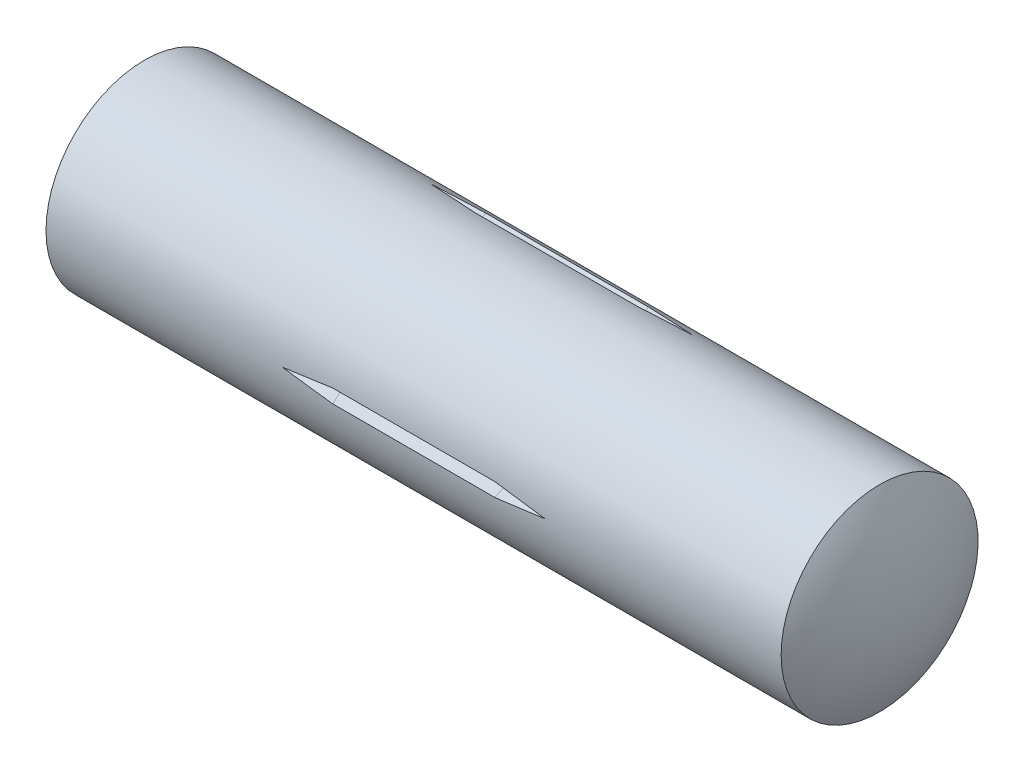
SolidWorks part; units mm, degrees
ref_plane "Plane1" through (0, 0, 0) normal (0, 0, 1) x (1, 0, 0)
ref_plane "Plane2" through (0, 0, 0) normal (0, 1, 0) x (1, 0, 0)
ref_plane "Plane3" through (0, 0, 0) normal (1, 0, 0) x (0, 0, -1)
sketch "Sketch1" plane through (0, 0, 0) normal (0, 0, 1) x (1, 0, 0)
  line L0 (-57, 0) -> (60, 0) construction
  line L1 (-50, 0) -> (-50, 1.25)
  line L2 (-46.6819, 12.5) -> (46.6506, 12.5)
  line L3 (-50, 0) -> (50, 0)
  arc A0 (-46.6819, 12.5) -> (-50, 1.25) centre (-25.0313, 0) ccw
  arc A1 (50, 0) -> (46.6506, 12.5) centre (25, 0) ccw
  dimension "D1" = 25
  dimension "D2" = 25
  dimension "Length" = 100
  dimension "D3" = 2.5
revolve "Base-Revolve" add sketch "Sketch1" angle 360 about L0
sketch "Sketch3" plane through (0, 0, 0) normal (0, 1, 0) x (1, 0, 0)
  line L0 (0, 0) -> (60, 0) construction
  line L1 (-57, 0) -> (60, 0) construction
  line L2 (-16.6667, -12.5) -> (-10.4167, -11.25)
  line L3 (-10.4167, -11.25) -> (10.4167, -11.25)
  line L4 (10.4167, -11.25) -> (16.6667, -12.5)
  dimension "D1" = 25
  dimension "D2" = 33.3333
  dimension "D3" = 16.6667
  dimension "D4" = 22.5
  dimension "D5" = 6.25
  dimension "D6" = 6.25
ref_plane "Plane4" through (-16.6667, 0, 0) normal (1, 0, 0) x (0, 0, -1)
sketch "Sketch4" plane through (-16.6667, 0, 0) normal (1, 0, 0) x (0, 0, -1)
  line L0 (0, 0) -> (-14, 0) construction
  line L1 (-12.5, 0) -> (-14.3784, 1.3152)
  line L2 (-12.5, 0) -> (-14.3784, -1.3152)
  line L3 (-14.3784, -1.3152) -> (-14.3784, 1.3152)
  circle A0 centre (0, 0) radius 12.5 construction
  dimension "D1" = 25
  dimension "D2" = 70
  dimension "D3" = 35
  dimension "D4" = 1.8784
sweep "Cut-Sweep3" cut profiles "Sketch4" path "Sketch3"
pattern_circular "CirPattern2" count 3 over 360 about axis through (-57, 0, 0) along (1, 0, 0) of "Cut-Sweep3"
equation "\"D1@Sketch1\" = \"Diameter@Sketch1\""
equation "\"D2@Sketch1\" = \"Diameter@Sketch1\""
equation "\"D3@Sketch1\" = \"Diameter@Sketch1\" * .1"
equation "\"D1@Sketch3\" = \"Diameter@Sketch1\""
equation "\"D2@Sketch3\" = \"Length@Sketch1\" / 3"
equation "\"D3@Sketch3\" = \"D2@Sketch3\" / 2"
equation "\"D4@Sketch3\" = \"Diameter@Sketch1\" * .9"
equation "\"D5@Sketch3\" = \"D1@Sketch1\" / 4"
equation "\"D6@Sketch3\" = \"D5@Sketch3\""
equation "\"D1@Plane4\" = \"D3@Sketch3\""
equation "\"D1@Sketch4\" = \"Diameter@Sketch1\""
equation "\"D3@Sketch4\" = \"D2@Sketch4\" / 2"
